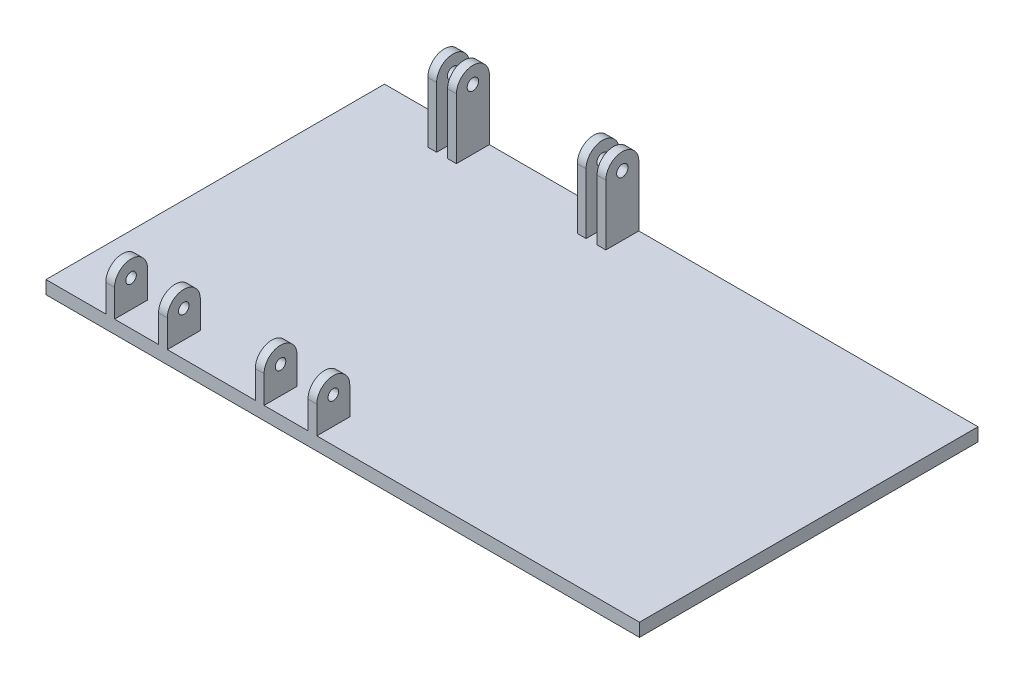
SolidWorks part; units mm, degrees
ref_plane "Front Plane" through (0, 0, 0) normal (0, 0, 1) x (1, 0, 0)
ref_plane "Top Plane" through (0, 0, 0) normal (0, 1, 0) x (1, 0, 0)
ref_plane "Right Plane" through (0, 0, 0) normal (1, 0, 0) x (0, 0, -1)
sketch "Sketch1" plane through (0, 0, 0) normal (0, 1, 0) x (1, 0, 0)
  line L1 (0, 0) -> (342.9, 0)
  line L2 (0, 0) -> (0, 195.58)
  line L3 (0, 195.58) -> (342.9, 195.58)
  line L4 (342.9, 0) -> (342.9, 195.58)
  dimension "D1" = 195.58
  dimension "D2" = 342.9
extrude "Boss-Extrude1" add sketch "Sketch1" along normal blind 7.62 contours L4 L3 L2 L1
sketch "Sketch2" plane through (0, 7.62, 0) normal (0, 1, 0) x (1, 0, 0)
  line L0 (0, 0) -> (342.9, 0) construction
  line L1 (34.5463, 0) -> (39.6263, 0)
  line L2 (34.5463, 0) -> (34.5463, 19.05)
  line L3 (34.5463, 19.05) -> (39.6263, 19.05)
  line L4 (39.6263, 0) -> (39.6263, 19.05)
  line L6 (65.0263, 0) -> (70.1063, 0)
  line L7 (65.0263, 0) -> (65.0263, 19.05)
  line L8 (65.0263, 19.05) -> (70.1063, 19.05)
  line L9 (70.1063, 0) -> (70.1063, 19.05)
  line L10 (120.9063, 0) -> (125.9863, 0)
  line L11 (120.9063, 0) -> (120.9063, 19.05)
  line L12 (120.9063, 19.05) -> (125.9863, 19.05)
  line L13 (125.9863, 0) -> (125.9863, 19.05)
  line L14 (151.3863, 0) -> (156.4663, 0)
  line L15 (151.3863, 0) -> (151.3863, 19.05)
  line L16 (151.3863, 19.05) -> (156.4663, 19.05)
  line L17 (156.4663, 0) -> (156.4663, 19.05)
  line L19 (0, 195.58) -> (342.9, 195.58) construction
  line L21 (49.1513, 195.58) -> (44.0713, 195.58)
  line L22 (49.1513, 195.58) -> (49.1513, 176.53)
  line L23 (49.1513, 176.53) -> (44.0713, 176.53)
  line L24 (44.0713, 195.58) -> (44.0713, 176.53)
  line L25 (55.5013, 195.58) -> (60.5813, 195.58)
  line L26 (55.5013, 195.58) -> (55.5013, 176.53)
  line L27 (55.5013, 176.53) -> (60.5813, 176.53)
  line L28 (60.5813, 195.58) -> (60.5813, 176.53)
  line L29 (130.4313, 195.58) -> (135.5113, 195.58)
  line L30 (130.4313, 195.58) -> (130.4313, 176.53)
  line L31 (130.4313, 176.53) -> (135.5113, 176.53)
  line L32 (135.5113, 195.58) -> (135.5113, 176.53)
  line L33 (141.8613, 195.58) -> (146.9413, 195.58)
  line L34 (141.8613, 195.58) -> (141.8613, 176.53)
  line L35 (141.8613, 176.53) -> (146.9413, 176.53)
  line L36 (146.9413, 195.58) -> (146.9413, 176.53)
  line M12 (0, 0) -> (342.9, 0)
  line M14 (342.9, 195.58) -> (0, 195.58)
  dimension "D1" = 19.05
  dimension "D2" = 5.08
  dimension "D3" = 25.4
  dimension "D4" = 5.08
  dimension "D5" = 19.05
  dimension "D6" = 50.8
  dimension "D7" = 5.08
  dimension "D8" = 19.05
  dimension "D9" = 25.4
  dimension "D10" = 5.08
  dimension "D11" = 19.05
  dimension "D12" = 6.35
  dimension "D13" = 5.08
  dimension "D14" = 5.08
  dimension "D15" = 5.08
  dimension "D16" = 19.05
  dimension "D17" = 19.05
  dimension "D18" = 5.08
  dimension "D19" = 6.35
extrude "Boss-Extrude2" add sketch "Sketch2" along normal blind 25.4 contours L4 L3 L2 M12 | L9 L8 L7 M12 | L17 L16 L15 M12 | L13 L12 L11 M12 region at (37.0863, 7.62, -9.525) region at (153.9263, 7.62, -9.525) region at (123.4463, 7.62, -9.525) region at (67.5663, 7.62, -9.525)
sketch "Sketch3" plane through (34.5463, 0, 0) normal (-1, 0, 0) x (0, 0, 1)
  line L0 (-19.05, 23.495) -> (-20.422, 33.02)
  line L1 (0, 33.02) -> (0, 7.62) construction
  line L2 (-20.422, 33.02) -> (2.9691, 35.8805)
  line L3 (-19.05, 33.02) -> (-19.05, 7.62) construction
  line L4 (2.9691, 35.8805) -> (0, 23.495)
  arc A0 (-19.05, 23.495) -> (0, 23.495) centre (-9.525, 23.495) cw
  circle A1 centre (-9.525, 23.495) radius 3.048
  dimension "D1" = 6.096
extrude "Cut-Extrude1" cut sketch "Sketch3" against normal through all
extrude "Boss-Extrude3" add sketch "Sketch2<4>" along normal blind 44.45 contours L24 L23 L22 M14 | L28 L26 L27 M14 | L36 L34 L35 M14 | L32 L30 L31 M14 region at (46.6113, 7.62, -186.055) region at (144.4013, 7.62, -186.055) region at (132.9713, 7.62, -186.055) region at (58.0413, 7.62, -186.055)
sketch "Sketch2<4>" plane through (0, 7.62, 0) normal (0, 1, 0) x (1, 0, 0) same geometry as "Sketch2"
sketch "Sketch4" plane through (44.0713, 0, 0) normal (-1, 0, 0) x (0, 0, 1)
  line L0 (-195.58, 42.545) -> (-197.5943, 55.0741)
  line L1 (-176.53, 52.07) -> (-176.53, 7.62) construction
  line L2 (-197.5943, 55.0741) -> (-172.1166, 54.4515)
  line L3 (-195.58, 52.07) -> (-195.58, 7.62) construction
  line L4 (-172.1166, 54.4515) -> (-176.53, 42.545)
  circle A0 centre (-186.055, 42.545) radius 3.302
  arc A1 (-195.58, 42.545) -> (-176.53, 42.545) centre (-186.055, 42.545) cw
  dimension "D1" = 6.604
extrude "Cut-Extrude2" cut sketch "Sketch4" against normal through all
